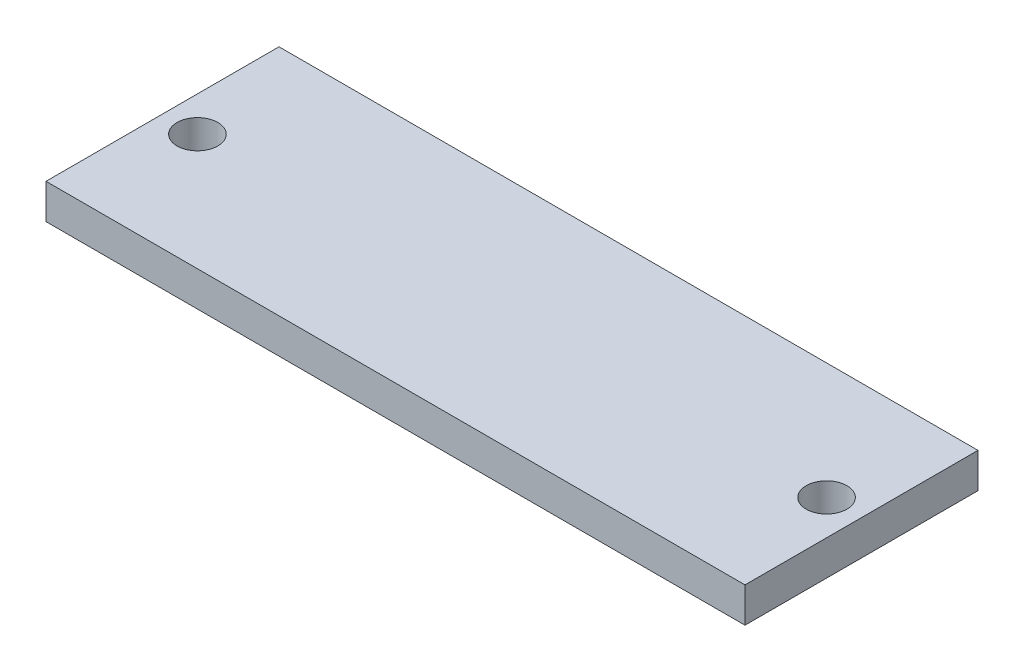
SolidWorks part; units mm, degrees
ref_plane "Front" through (0, 0, 0) normal (0, 0, 1) x (1, 0, 0)
ref_plane "Top" through (0, 0, 0) normal (0, 1, 0) x (1, 0, 0)
ref_plane "Right" through (0, 0, 0) normal (1, 0, 0) x (0, 0, -1)
sketch "Esquisse1" plane through (0, 0, 0) normal (0, 1, 0) x (1, 0, 0)
  line L1 (60, -20) -> (-60, -20)
  line L2 (60, -20) -> (60, 20)
  line L3 (60, 20) -> (-60, 20)
  line L4 (-60, -20) -> (-60, 20)
  line L5 (60, -20) -> (-60, 20) construction
  line L6 (60, 20) -> (-60, -20) construction
  point P0 (0, 0)
  dimension "D1" = 40
  dimension "D2" = 120
base flange "Tôle de base pliée1" sketch "Esquisse1" thickness 6 reverse thickness direction no parameters "D1"=0.7366
hole_wizard "Dégagement M61" positions "Esquisse2" profile "Esquisse3" hole size "M6" standard "ISO" end condition through all
sketch "Esquisse2" plane through (0, 0, 0) normal (0, 1, 0) x (1, 0, 0)
  line L2 (54, -14) -> (-54, -14) construction
  line L3 (54, -14) -> (54, 14) construction
  line L4 (54, 14) -> (-54, 14) construction
  line L5 (-54, -14) -> (-54, 14) construction
  line L6 (54, -14) -> (-54, 14) construction
  line L7 (54, 14) -> (-54, -14) construction
  line L8 (60, 20) -> (-60, 20) construction
  line L9 (-60, 20) -> (-60, -20) construction
  point P88 (-54, 0)
  point P90 (54, 0)
  dimension "D1" = 6
  dimension "D2" = 6
sketch "Esquisse3" plane through (54, 0, 0) normal (1, 0, 0) x (0, 0, 1)
  line L0 (0, 0) -> (0, 6)
  line L1 (0, 6) -> (3.5, 6)
  line L2 (3.5, 6) -> (3.5, 0)
  line L5 (3.5, 0) -> (0, 0)
  line L11 (0, -6.35) -> (0, 107.95) construction
  dimension "Diamètre du perçage jusqu'au prochain" = 7
  dimension "Profondeur du perçage jusqu'au prochain" = 6
sketch "Lignes de pliage1" [suppressed] plane through (0, 0, 0) normal (0, 1, 0) x (1, 0, 0)
sketch "Cube de visualisation1" [suppressed] plane through (0, 0, 0) normal (0, 1, 0) x (1, 0, 0)
sheet metal parameters "Tôlerie1" thickness 6 parameters "D1"=0.7366
flat pattern "Etat déplié1" [suppressed]
sketch "Lignes de pliage2" plane through (0, 0, 0) normal (0, 1, 0) x (1, 0, 0)
sketch3d "Cube de visualisation2" [suppressed]
  line L0 (-75, -20, 0) -> (75, -20, 0) construction
  line L1 (-75, 20, 0) -> (75, 20, 0) construction
  line L2 (-75, -20, 0) -> (-75, 20, 0) construction
  line L3 (75, -20, 0) -> (75, 20, 0) construction
sheet metal parameters "Tôlerie2" thickness 6 parameters "D1"=0.7366
flat pattern "Etat déplié1"
sketch "Lignes de pliage2" plane through (0, 0, 0) normal (0, 1, 0) x (1, 0, 0)
sketch3d "Cube de visualisation2" [suppressed]
  line L0 (60, -20, 0) -> (-60, -20, 0) construction
  line L1 (60, 20, 0) -> (-60, 20, 0) construction
  line L2 (60, -20, 0) -> (60, 20, 0) construction
  line L3 (-60, -20, 0) -> (-60, 20, 0) construction
